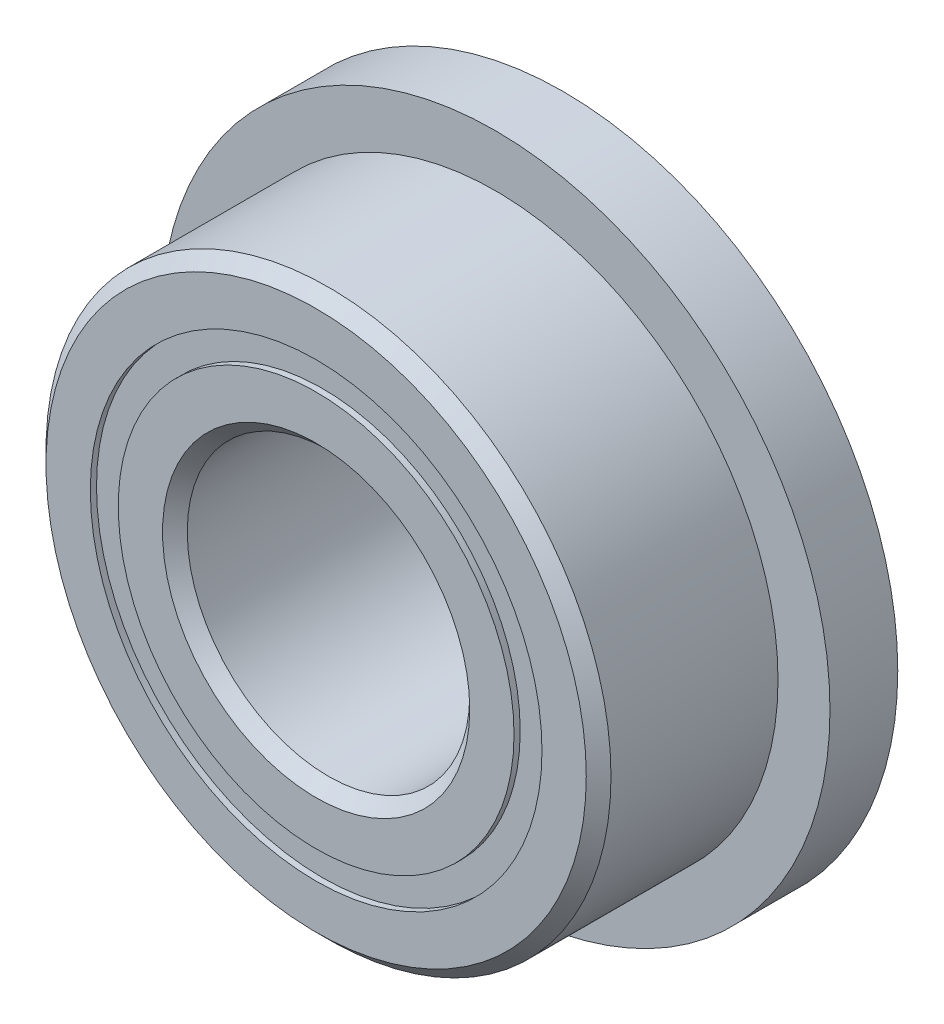
SolidWorks part; units mm, degrees
ref_plane "Front Plane" through (0, 0, 0) normal (0, 0, 1) x (1, 0, 0)
ref_plane "Top Plane" through (0, 0, 0) normal (0, 1, 0) x (1, 0, 0)
ref_plane "Right Plane" through (0, 0, 0) normal (1, 0, 0) x (0, 0, -1)
sketch "Sketch1" plane through (0, 0, 0) normal (1, 0, 0) x (0, 0, -1)
  line L0 (-1.3891, 0) -> (1.3891, 0) construction
  line L1 (0, 3.175) -> (0, -3.175) construction
  line L2 (1.3891, 3.175) -> (-1.3891, 3.175) construction
  line L9 (0, 3.175) -> (0, 2.3812) construction
  line L10 (0, 2.3812) -> (0, 1.5875) construction
  point P14 (0, 1.5875)
  dimension "Width" = 2.7781
  dimension "OD" = 6.35
  dimension "Shaft Dia" = 3.175
sketch "Sketch2" plane through (0, 0, 0) normal (1, 0, 0) x (0, 0, -1)
  line L0 (1.9844, 0) -> (-1.9844, 0) construction
  line L1 (1.3891, 2.5383) -> (0.6271, 2.5383) construction
  line L2 (1.3891, 2.5383) -> (1.3891, 3.7592) construction
  line L3 (1.3891, 3.7592) -> (0.6271, 3.7592) construction
  line L4 (0.6271, 2.5383) -> (0.6271, 3.7592) construction
  dimension "Th" = 0.762
  dimension "Flange OD" = 7.5184
  dimension "D1" = 0.157
sketch "Sketch" plane through (0, 0, 0) normal (1, 0, 0) x (0, 0, -1)
  line L0 (-1.3891, 0) -> (1.3891, 0) construction
  line L1 (0, 3.175) -> (0, -3.175) construction
  line L2 (1.2502, 3.175) -> (-1.2502, 3.175)
  line L3 (-1.2502, 3.175) -> (-1.3891, 3.0361)
  line L4 (-1.3891, 3.0361) -> (-1.3891, 2.5383)
  line L5 (-1.3891, 2.5383) -> (-0.6174, 2.5383)
  line L6 (1.3891, 2.5383) -> (0.6174, 2.5383)
  line L7 (1.3891, 3.0361) -> (1.3891, 2.5383)
  line L8 (1.2502, 3.175) -> (1.3891, 3.0361)
  line L9 (0, 3.175) -> (0, 2.3812) construction
  line L10 (0, 2.3812) -> (0, 1.5875) construction
  arc A0 (-0.6174, 2.5383) -> (0.6174, 2.5383) centre (0, 2.3812) cw
  point P14 (0, 1.5875)
  dimension "D1" = 45
  dimension "D2" = 0.1389
  dimension "D3" = 1.2347
  dimension "D4" = 0.157
revolve "Revolve1" add sketch "Sketch" angle 360 about L0
sketch "Sketch3" plane through (0, 0, 0) normal (1, 0, 0) x (0, 0, -1)
  line L0 (-1.3891, 2.2242) -> (-0.6174, 2.2242)
  line L1 (0, 3.175) -> (0, -3.175) construction
  line L2 (-1.3891, 3.0361) -> (-1.3891, 2.5383) construction
  line L3 (-1.3891, 2.2242) -> (-1.3891, 1.7264)
  line L4 (-1.2502, 3.175) -> (-1.3891, 3.0361) construction
  line L5 (-1.3891, 1.7264) -> (-1.2502, 1.5875)
  line L6 (-1.2502, 1.5875) -> (1.2502, 1.5875)
  line L7 (1.2502, 3.175) -> (1.2502, -3.175) construction
  line L8 (1.2502, 1.5875) -> (1.3891, 1.7264)
  line L9 (1.3891, -3.0361) -> (1.3891, 3.0361) construction
  line L10 (1.3891, 1.7264) -> (1.3891, 2.2242)
  line L11 (1.3891, 2.2242) -> (0.6174, 2.2242)
  line L13 (1.2502, 3.175) -> (1.3891, 3.0361) construction
  arc A0 (0.6174, 2.5383) -> (-0.6174, 2.5383) centre (0, 2.3812) ccw construction
  arc A1 (0.6174, 2.2242) -> (-0.6174, 2.2242) centre (0, 2.3812) cw
revolve "Revolve3" add sketch "Sketch3" angle 360 about L0
sketch "Sketch4" plane through (0, 0, 0) normal (1, 0, 0) x (0, 0, -1)
  line L0 (-0.637, 2.3812) -> (0.637, 2.3812)
  arc A2 (-0.637, 2.3812) -> (0.637, 2.3812) centre (0, 2.3812) cw
  arc A3 (0.6174, 2.5383) -> (-0.6174, 2.5383) centre (0, 2.3812) ccw construction
revolve "Revolve4" add sketch "Sketch4" angle 360 about L0
ref_axis "Axis1" through (0, 0, -1.3891) along (0, 0, 1)
pattern_circular "CirPattern1" count 10 every 36 about axis through (0, 0, -1.3891) along (0, 0, 1) of bodies 104
sketch "Sketch5" plane through (0, 0, 0) normal (1, 0, 0) x (0, 0, -1)
  line L0 (-1.3891, 2.5383) -> (-0.6174, 2.5383) construction
  line L1 (-1.3196, 2.5383) -> (-0.637, 2.5383)
  line L2 (-1.3196, 2.5383) -> (-1.3196, 2.2242)
  line L3 (-1.3196, 2.2242) -> (-0.637, 2.2242)
  line L4 (-0.637, 2.5383) -> (-0.637, 2.2242)
  line L5 (-1.3891, 2.2242) -> (-0.6174, 2.2242) construction
  line L6 (1.3891, 2.5383) -> (0.6174, 2.5383) construction
  line L7 (1.3196, 2.5383) -> (0.637, 2.5383)
  line L8 (1.3196, 2.5383) -> (1.3196, 2.2242)
  line L9 (1.3196, 2.2242) -> (0.637, 2.2242)
  line L10 (0.637, 2.5383) -> (0.637, 2.2242)
  line L11 (1.3891, 2.2242) -> (0.6174, 2.2242) construction
  line L12 (-1.2502, 3.175) -> (-1.3891, 3.0361) construction
  point P18 (-1.3196, 3.1055)
revolve "Revolve5" add sketch "Sketch5" angle 360 about L0
sketch "Sketch6" plane through (0, 0, 0) normal (1, 0, 0) x (0, 0, -1)
  line L0 (1.3891, 0) -> (-1.3891, 0) construction
  line L1 (1.3891, 2.5383) -> (0.6271, 2.5383)
  line L2 (1.3891, 2.5383) -> (1.3891, 3.7592)
  line L3 (1.3891, 3.7592) -> (0.6271, 3.7592)
  line L4 (0.6271, 2.5383) -> (0.6271, 3.7592)
  dimension "Th" = 0.762
  dimension "Flange OD" = 7.5184
revolve "Revolve6" add sketch "Sketch6" angle 360 about L0
sketch "Sketch7" plane through (0, 0, 0) normal (1, 0, 0) x (0, 0, -1)
  line L1 (1.3891, 3.175) -> (-1.3891, 3.175) construction
  line L2 (1.3891, 3.175) -> (-1.3891, 3.175) construction
  line L3 (1.3891, -3.175) -> (-1.3891, -3.175) construction
  line L4 (1.3891, -3.7592) -> (1.3891, 3.7592) construction
  line L5 (1.3891, 3.175) -> (1.3891, 3.7592) construction
  line L6 (1.3891, 3.7592) -> (0.6271, 3.7592) construction
  dimension "D1" = 6.35
  dimension "D2" = 2.7781
sketch "Sketch8" plane through (0, 0, 0) normal (0, 0, 1) x (1, 0, 0)
  circle A0 centre (0, 0) radius 1.5875 construction
  dimension "D1" = 3.175
equation "\"D2@Sketch\" = \"Width@Sketch1\" * .05"
equation "\"D3@Sketch\" = \"Width@Sketch1\" / 2.25"
equation "\"D4@Sketch\"=(  (  ( \"OD@Sketch1\" - \"Width@Sketch1\" )  / 2 )  / 3.25 )  / 3.5"
equation "\"D2@CirPattern1\" = 360/\"Balls@CirPattern1\""
equation "\"D1@Sketch2\"=(  (  ( \"OD@Sketch1\" - \"Width@Sketch1\" )  / 2 )  / 3.25 )  / 3.5"
